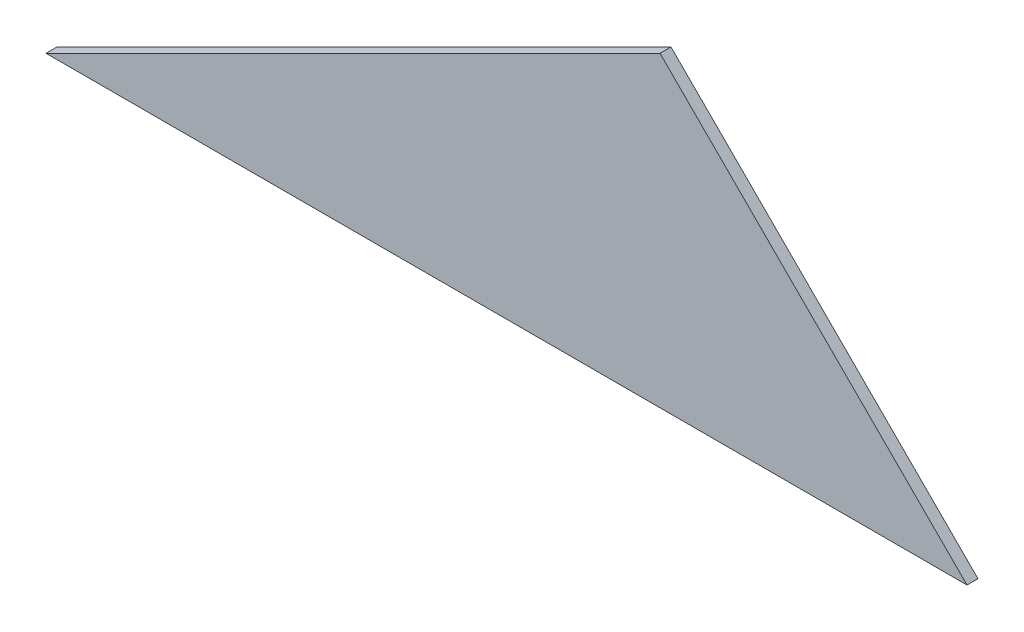
SolidWorks part; units mm, degrees
ref_plane "Front Plane" through (0, 0, 0) normal (0, 0, 1) x (1, 0, 0)
ref_plane "Top Plane" through (0, 0, 0) normal (0, 1, 0) x (1, 0, 0)
ref_plane "Right Plane" through (0, 0, 0) normal (1, 0, 0) x (0, 0, -1)
sketch "Sketch2" plane through (0, 0, 0) normal (0, 0, 1) x (1, 0, 0)
  line L0 (0, 0) -> (210, 0)
  line L1 (210, 0) -> (140, 70)
  line L2 (140, 70) -> (0, 0)
  dimension "D1" = 210
  dimension "D2" = 140
  dimension "D3" = 70
extrude "Boss-Extrude1" add sketch "Sketch2" along normal blind 2.5
ref_axis "Axis1" through (140, 70, 2.5) along (0, 0, -1)
ref_axis "Axis2" through (210, 0, 2.5) along (0, 0, -1)
